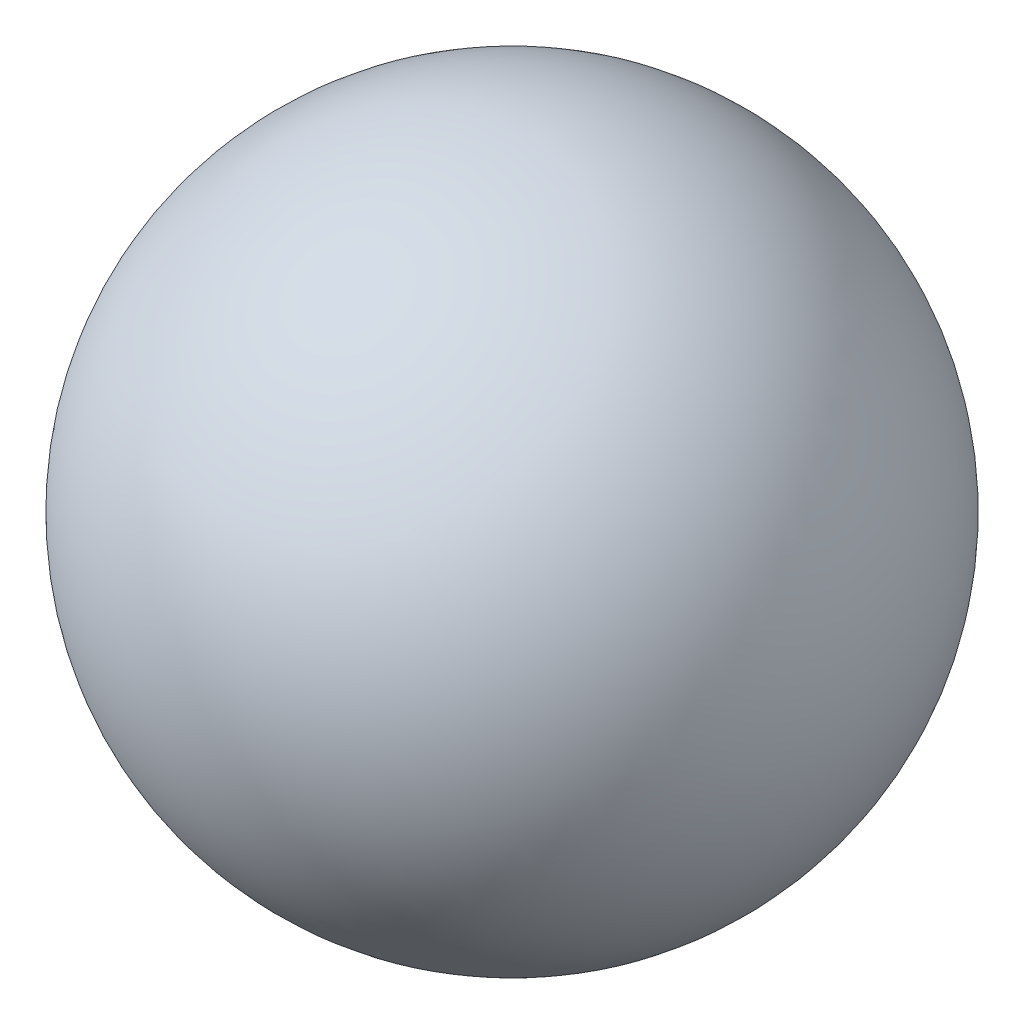
SolidWorks part; units mm, degrees
material "ｼﾘｺﾝ ｺﾞﾑ"
ref_plane "正面" through (0, 0, 0) normal (0, 0, 1) x (1, 0, 0)
ref_plane "平面" through (0, 0, 0) normal (0, 1, 0) x (1, 0, 0)
ref_plane "右側面" through (0, 0, 0) normal (1, 0, 0) x (0, 0, -1)
sketch "ｽｹｯﾁ1" plane through (0, 0, 0) normal (0, 0, 1) x (1, 0, 0)
  line L0 (0, -55) -> (0, 55) construction
  line L1 (0, 125) -> (0, -125)
  arc A0 (0, 125) -> (0, -125) centre (0, 0) cw
  point P6 (0, 125)
  point P7 (0, -125)
  dimension "D1" = 250
revolve "回転1" add sketch "ｽｹｯﾁ1" angle 360 about L1 region at (53.0516, 0, 0)
